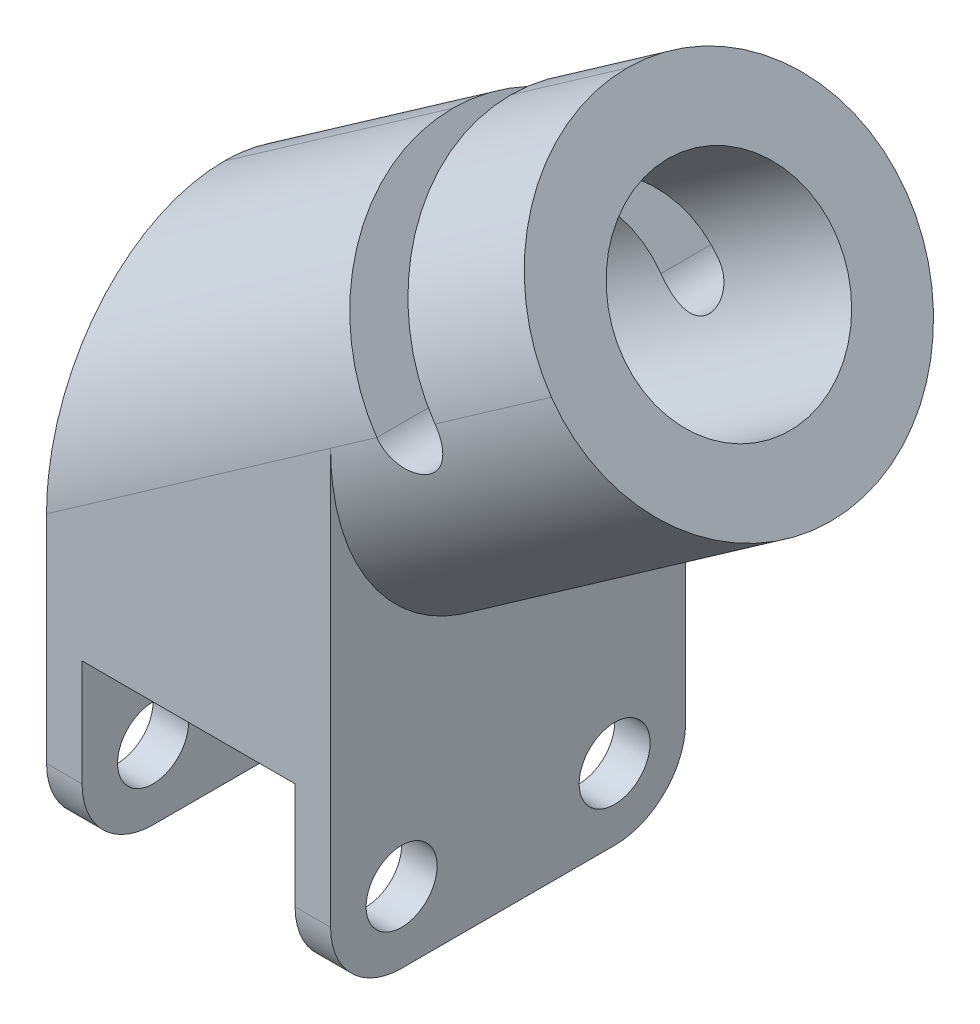
SolidWorks part; units mm, degrees
ref_plane "Front Plane" through (0, 0, 0) normal (0, 0, 1) x (1, 0, 0)
ref_plane "Top Plane" through (0, 0, 0) normal (0, 1, 0) x (1, 0, 0)
ref_plane "Right Plane" through (0, 0, 0) normal (1, 0, 0) x (0, 0, -1)
sketch "Sketch1" plane through (0, 0, 0) normal (0, 0, 1) x (1, 0, 0)
  line L0 (5, 0) -> (35, 0)
  line L2 (429.3521, 329.4883) -> (421.3212, 340.9576)
  line L3 (56.7515, 85.6832) -> (40, 73.9536)
  line L4 (0, 45.9453) -> (0, 0)
  line L5 (0, 0) -> (0, -25)
  line L6 (0, -25) -> (5, -25)
  line L7 (5, -25) -> (5, 0)
  line L8 (5, 0) -> (35, 0)
  line L9 (35, 0) -> (35, -25)
  line L10 (35, -25) -> (40, -25)
  line L11 (40, -25) -> (40, 0)
  line L12 (40, 0) -> (40, 57.3034) construction
  line L13 (35, 0) -> (35, 9.4139) construction
  line L14 (85.4303, 44.7256) -> (40, 12.9149) construction
  line L15 (35, 5) -> (0, 5) construction
  line L16 (35, 12.1407) -> (7.6024, 51.2686) construction
  line L17 (7.6024, 51.2686) -> (35, 70.4526) construction
  line L18 (56.7515, 85.6832) -> (85.4303, 44.7256) construction
  line L19 (56.7515, 85.6832) -> (85.4303, 44.7256)
  line L20 (85.4303, 44.7256) -> (40, 12.9149)
  line L21 (40, 12.9149) -> (40, 0)
  line L22 (50.6121, 50.865) -> (64.9515, 30.3862) construction
  line L23 (36.2812, 10.311) -> (35, 9.4139) construction
  line L24 (40.3685, 74.2116) -> (54.7079, 53.7328)
  line L25 (32.1769, 68.4759) -> (46.5164, 47.9971)
  line L26 (35, 70.4526) -> (0, 45.9453)
  line L27 (40, 73.9536) -> (56.7515, 85.6832) construction
  line L28 (35, 12.1407) -> (35, 70.4526) construction
  arc A0 (26.0291, 94.6904) -> (17.8375, 88.9547) centre (21.9333, 91.8226) ccw
  arc A1 (46.5164, 47.9971) -> (54.7079, 53.7328) centre (50.6121, 50.865) ccw
  point P25 (36.2727, 71.3438)
  dimension "D2" = 50
  dimension "D3" = 25
  dimension "D5" = 125
  dimension "D6" = 25
  dimension "D7" = 25
  dimension "D8" = 30
  dimension "D9" = 5
  dimension "D10" = 5
  dimension "D11" = 5
  dimension "D12" = 60
extrude "Boss-Extrude1" add sketch "Sketch1" along normal blind 50 contours A1 L25 L26 L4 L5 L6 L7 L0 L9 L10 L11 L21 L20 L19 L3 L24 region at (35.5463, 34.8884, 0)
sketch "Sketch2" plane through (78.3388, 54.8534, 0) normal (0.8192, 0.5736, 0) x (0, 0, -1)
  line L0 (0, 12.6362) -> (-50, 12.6362) construction
  line L1 (0, 37.6362) -> (0, -12.3638) construction
  circle A0 centre (-25, 12.6362) radius 15
extrude "Cut-Extrude1" cut sketch "Sketch2" against normal blind 60
chamfer "Chamfer1" distance 5 angle 45 1 edges at (13.3382, 43.0771, 25)
sketch "Sketch3" plane through (5, 0, 0) normal (1, 0, 0) x (0, 0, -1)
  line L0 (0, 0) -> (-50, 0) construction
  line L1 (-50, 0) -> (0, 0) construction
  line L2 (-50, 0) -> (-50, -15) construction
  line L3 (-50, -15) -> (0, -15) construction
  line L4 (0, -25) -> (0, 0) construction
  line L5 (0, -15) -> (-25, -15) construction
  line L6 (-25, -15) -> (-25, 0) construction
  circle A0 centre (-40, -15) radius 5
  circle A1 centre (-10, -15) radius 5
  dimension "D2" = 15
  dimension "D3" = 10
  dimension "D1" = 15
extrude "Cut-Extrude2" cut sketch "Sketch3" against normal through all both and the other way through all
fillet "Fillet2" radius 10 4 edges at (2.5, -25, 50) (37.5, -25, 50) (2.5, -25, 0) (37.5, -25, 0)
fillet "Fillet3" radius 25 6 edges at (16.0885, 57.2106, 0) (48.56, 79.9474, 0) (62.7152, 28.8202, 0) (48.56, 79.9474, 50) (16.0885, 57.2106, 50) (62.7152, 28.8202, 50)
